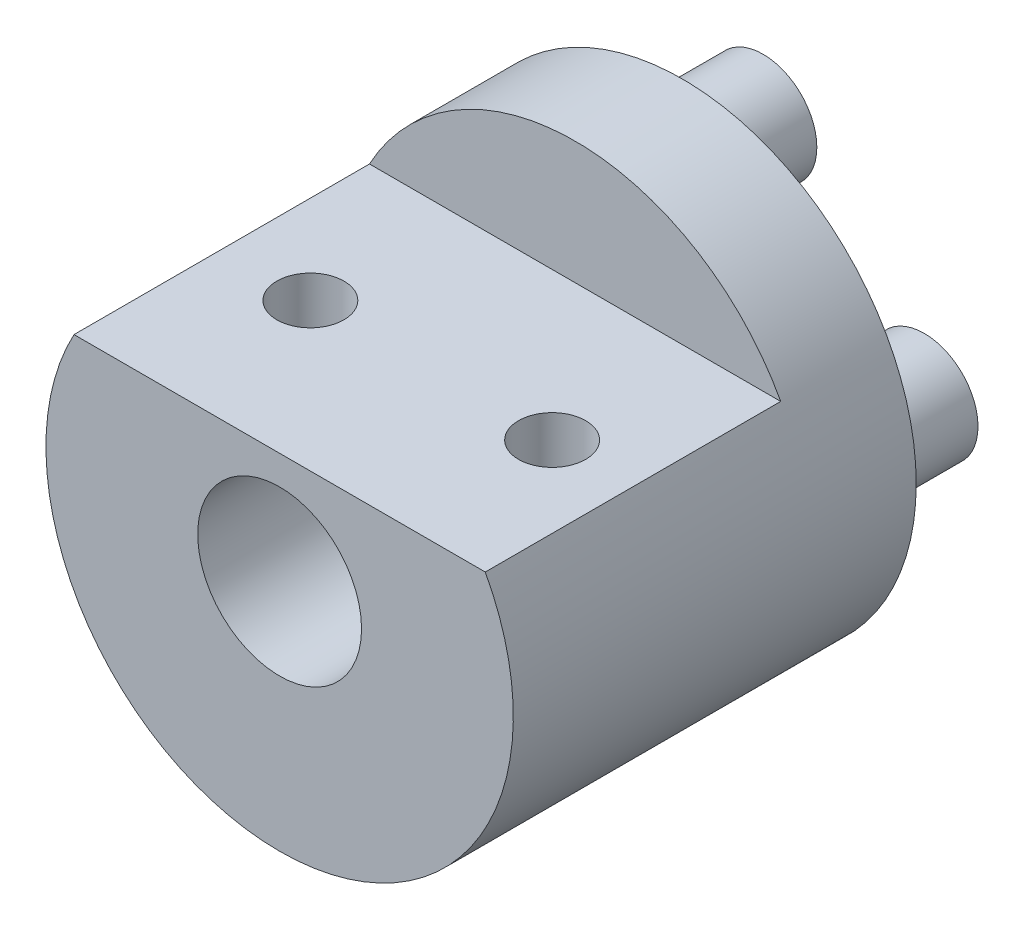
SolidWorks part; units mm, degrees
ref_plane "Front Plane" through (0, 0, 0) normal (0, 0, 1) x (1, 0, 0)
ref_plane "Top Plane" through (0, 0, 0) normal (0, 1, 0) x (1, 0, 0)
ref_plane "Right Plane" through (0, 0, 0) normal (1, 0, 0) x (0, 0, -1)
sketch "Sketch1" plane through (0, 0, 0) normal (0, 0, 1) x (1, 0, 0)
  circle A0 centre (0, 0) radius 8.7
  dimension "D1" = 17.4
extrude "Boss-Extrude1" add sketch "Sketch1" along normal blind 15 contours A0
sketch "Sketch2" plane through (0, 0, 15) normal (0, 0, 1) x (1, 0, 0)
  line L1 (-7.6555, 8.7) -> (9.3445, 8.7)
  line L2 (-7.6555, 8.7) -> (-7.6555, 4.1331)
  line L3 (-7.6555, 4.1331) -> (9.3445, 4.1331)
  line L4 (9.3445, 8.7) -> (9.3445, 4.1331)
  circle A0 centre (0, 0) radius 8.7 construction
  dimension "D1" = 17
sketch "Sketch4" plane through (0, 0, 0) normal (0, 0, -1) x (-1, 0, 0)
  circle A0 centre (0, 6) radius 2
  circle A1 centre (6, 0) radius 2
  circle A2 centre (0, -6) radius 2
  circle A3 centre (-6, 0) radius 2
  dimension "D1" = 4
  dimension "D2" = 6
  dimension "D3" = 6
  dimension "D4" = 6
  dimension "D5" = 6
sketch "Sketch5" plane through (0, 0, 0) normal (0, 0, -1) x (-1, 0, 0)
  circle A0 centre (0, 0) radius 1.75
  dimension "D1" = 3.5
extrude "Cut-Extrude1" cut sketch "Sketch5" against normal through all
sketch "Sketch6" plane through (0, 0, 15) normal (0, 0, 1) x (1, 0, 0)
  circle A0 centre (0, 0) radius 3.05
  dimension "D1" = 6.1
extrude "Cut-Extrude3" cut sketch "Sketch6" against normal offset from surface (12 mm away) 3 up to face at (-1.75, 0, 0)
extrude "Cut-Extrude4" cut sketch "Sketch2" against normal blind 11 contours L1 L4 L3 L2
fillet "Fillet1" radius 0.3 1 edges at (1.75, 0, 3)
hole_wizard "Tap Drill for M3x0.5 Tap1" positions "Sketch11" profile "Sketch12" hole size "M3x0.5" standard "ANSI Metric" end condition through all
sketch "Sketch11" plane through (0, 4.1331, 0) normal (0, 1, 0) x (1, 0, 0)
  line L0 (-7.6555, -15) -> (7.6555, -15) construction
  line L1 (-7.6555, -4) -> (-7.6555, -15) construction
  point P0 (-4.3555, -9.5)
  point P2 (4.6445, -9.5)
  dimension "D1" = 9
  dimension "D2" = 5.5
  dimension "D3" = 3.3
sketch "Sketch12" plane through (-4.3555, 4.1331, 9.5) normal (1, 0, 0) x (0, 0, 1)
  line L0 (0, 0) -> (0, 12.8331)
  line L1 (0, 12.8331) -> (1.25, 12.8331)
  line L2 (1.25, 12.8331) -> (1.25, 0)
  line L5 (1.25, 0) -> (0, 0)
  line L11 (0, -6.35) -> (0, 107.95) construction
  dimension "Thru Hole Dia." = 2.5
  dimension "Thru Hole Depth" = 12.8331
extrude "Boss-Extrude2" add sketch "Sketch4" along normal blind 3
